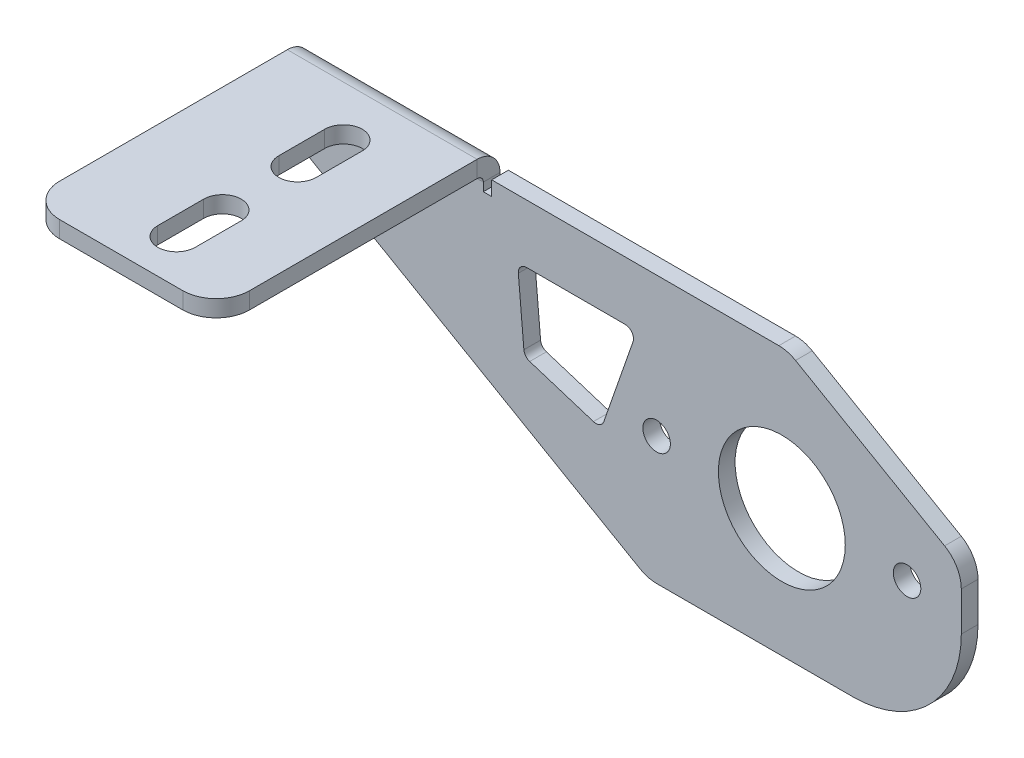
SolidWorks part; units mm, degrees
note: The reader was unsure of these and kept them because the rebuilt part matched: flange length of "边线-法兰1".
material "6061 合金"
ref_plane "前视基准面" through (0, 0, 0) normal (0, 0, 1) x (1, 0, 0)
ref_plane "上视基准面" through (0, 0, 0) normal (0, 1, 0) x (1, 0, 0)
ref_plane "右视基准面" through (0, 0, 0) normal (1, 0, 0) x (0, 0, -1)
sketch "草图1" plane through (0, 0, 0) normal (0, 0, 1) x (1, 0, 0)
  line L0 (0, 0) -> (0, -7.5)
  line L1 (0, -7.5) -> (42.4352, -32)
  line L2 (42.4352, -32) -> (80, -32)
  line L3 (80, -32) -> (80, -12)
  line L4 (80, -12) -> (59.2154, 0)
  line L5 (59.2154, 0) -> (0, 0)
  dimension "D1" = 7.5
  dimension "D2" = 20
  dimension "D3" = 80
  dimension "D4" = 150
  dimension "D5" = 120
  dimension "D6" = 32
base flange "基体-法兰1" sketch "草图1" thickness 2 reverse thickness direction no parameters "D1"=0.7366
sketch "草图6" plane through (0, 0, 0) normal (0, 0, 1) x (1, 0, 0)
  line L0 (80, -32) -> (80, -12) construction
  line L1 (42.4352, -32) -> (80, -32) construction
  circle A0 centre (58.5, -16.7) radius 7.6
  circle A1 centre (73.5, -16.7) radius 1.65
  circle A2 centre (43.5, -16.7) radius 1.65
  dimension "D1" = 15.2
  dimension "D4" = 3.3
  dimension "D5" = 3.3
  dimension "D2" = 21.5
  dimension "D3" = 15.3
  dimension "D6" = 15
  dimension "D7" = 15
extrude "切除-拉伸1" cut sketch "草图6" against normal blind 10 normal cut yes
edge flange "边线-法兰1" sketch "草图9" flange angle 90 flange length 34 flange position material outside bend radius 0.7366 thickness 2 relief rectangular parameters "D6"=10
sketch "草图9" plane through (0, 0, 0) normal (0, 1, 0) x (-1, 0, 0)
  line L0 (-59.2154, 0) -> (0, 0) construction
  line L2 (-22.74, 0) -> (-22.74, 32)
  line L3 (-22.74, 32) -> (0, 32)
  line L4 (0, 32) -> (0, 0)
  line L5 (-22.74, 0) -> (0, 0)
  dimension "D1" = 22.74
  dimension "D2" = 32
bend "边线折弯1" bend radius 0.7366 bend angle 90 parameters "D5"=1
sketch "草图12" plane through (0, 2, 0) normal (0, 1, 0) x (1, 0, 0)
  line L0 (12.74, -32) -> (12.74, -0.7366) construction
  line L1 (0, -32) -> (22.74, -32) construction
  line L2 (0, -0.7366) -> (22.74, -0.7366) construction
  line L3 (22.74, -32) -> (22.74, -0.7366) construction
  line L4 (12.74, -26.75) -> (12.74, -21.25) construction
  line L5 (10.49, -26.75) -> (10.49, -21.25)
  line L6 (14.99, -26.75) -> (14.99, -21.25)
  line L7 (12.74, -12.25) -> (12.74, -6.75) construction
  line L8 (10.49, -12.25) -> (10.49, -6.75)
  line L9 (14.99, -12.25) -> (14.99, -6.75)
  arc A0 (10.49, -26.75) -> (14.99, -26.75) centre (12.74, -26.75) ccw
  arc A1 (14.99, -21.25) -> (10.49, -21.25) centre (12.74, -21.25) ccw
  arc A2 (10.49, -12.25) -> (14.99, -12.25) centre (12.74, -12.25) ccw
  arc A3 (14.99, -6.75) -> (10.49, -6.75) centre (12.74, -6.75) ccw
  point P10 (12.74, -24)
  point P15 (12.74, -9.5)
  point P22 (12.74, -19)
  point P23 (12.74, -14.5)
  dimension "D4" = 2.25
  dimension "D5" = 2.25
  dimension "D1" = 10
  dimension "D2" = 5.5
  dimension "D3" = 5.5
  dimension "D6" = 5.25
  dimension "D7" = 4.5
extrude "切除-拉伸2" cut sketch "草图12" against normal blind 10 normal cut yes
fillet "圆角1" radius 4 6 edges at (59.2154, 0, -1) (80, -12, -1) (42.4352, -32, -1) (0, -7.5, -1) (22.74, 1, 32) (0, 1, 32)
unfold "展开1" [suppressed]
sketch "草图12-1" plane through (0, 1.2546, -2) normal (0, 0, -1) x (1, 0, 0)
  line L0 (12.74, -32) -> (12.74, -0.7366) construction
  line L1 (4, -32) -> (18.74, -32) construction
  line L3 (22.74, -28) -> (22.74, -0.7366) construction
  line L4 (12.74, -26.75) -> (12.74, -21.25) construction
  line L5 (10.49, -26.75) -> (10.49, -21.25)
  line L6 (14.99, -26.75) -> (14.99, -21.25)
  line L7 (12.74, -12.25) -> (12.74, -6.75) construction
  line L8 (10.49, -12.25) -> (10.49, -6.75)
  line L9 (14.99, -12.25) -> (14.99, -6.75)
  arc A0 (10.49, -26.75) -> (14.99, -26.75) centre (12.74, -26.75) ccw
  arc A1 (14.99, -21.25) -> (10.49, -21.25) centre (12.74, -21.25) ccw
  arc A2 (10.49, -12.25) -> (14.99, -12.25) centre (12.74, -12.25) ccw
  arc A3 (14.99, -6.75) -> (10.49, -6.75) centre (12.74, -6.75) ccw
  point P10 (12.74, -24)
  point P15 (12.74, -9.5)
  dimension "D4" = 2.25
  dimension "D5" = 2.25
  dimension "D1" = 10
  dimension "D2" = 5.5
  dimension "D3" = 5.5
  dimension "D6" = 5.25
sketch "草图14" plane through (0, 0, -2) normal (0, 0, -1) x (-1, 0, 0)
  line L0 (-36.8593, -19.275) -> (-27.6593, -16.3642)
  line L1 (-27.6593, -16.3642) -> (-26.84, -7)
  line L2 (-26.84, -7) -> (-41.14, -7)
  line L3 (-41.14, -7) -> (-36.8593, -19.275)
  line L4 (-58.1436, 0) -> (-23.74, 0) construction
  line L5 (-22.74, -1.7366) -> (-22.74, -0.7366) construction
  dimension "D1" = 14.3
  dimension "D2" = 85
  dimension "D3" = 9.4
  dimension "D4" = 13
  dimension "D5" = 7
  dimension "D6" = 4.1
  dimension "D7" = 9.2
extrude "切除-拉伸3" cut sketch "草图14" against normal blind 10 normal cut yes
fillet "圆角2" radius 1 4 edges at (26.84, -7, -1) (27.6593, -16.3642, -1) (36.8593, -19.275, -1) (41.14, -7, -1)
fillet "圆角3" radius 13 1 edges at (80, -32, -1)
sketch "折弯-线1" plane through (0, 0, 0) normal (0, 1, 0) x (1, 0, 0)
sketch "边界框1" plane through (0, 0, 0) normal (0, 1, 0) x (1, 0, 0)
sheet metal parameters "钣金1" thickness 2 parameters "D1"=0.7366
flat pattern "平板型式1"
sketch "折弯-线2" plane through (0, 0, 0) normal (0, 1, 0) x (1, 0, 0)
sketch3d "边界框2"
  line L0 (0, -28.2, 0) -> (-70.5, -28.2, 0) construction
  line L1 (0, 0, 0) -> (-70.5, 0, 0) construction
  line L2 (0, -28.2, 0) -> (0, 0, 0) construction
  line L3 (-70.5, -28.2, 0) -> (-70.5, 0, 0) construction
sheet metal parameters "钣金2" thickness 2 parameters "D1"=0.7366
flat pattern "平板型式1"
sketch "折弯-线2" plane through (0, 0, 0) normal (0, 1, 0) x (1, 0, 0)
sketch3d "边界框2"
  line L0 (0, -28.2, 0) -> (70.5, -28.2, 0) construction
  line L1 (0, 0, 0) -> (70.5, 0, 0) construction
  line L2 (0, -28.2, 0) -> (0, 0, 0) construction
  line L3 (70.5, -28.2, 0) -> (70.5, 0, 0) construction
sheet metal parameters "钣金3" thickness 2 parameters "D1"=0.7366
flat pattern "平板型式1"
sketch "折弯-线2" plane through (0, 0, 0) normal (0, 0, 1) x (1, 0, 0)
  line L0 (22.74, 0.6273) -> (0, 0.6273) construction
  line L1 (22.74, 0.6273) -> (0, 0.6273) construction
sketch3d "边界框2"
  line L0 (10.556, 44.5955, 0) -> (78.9782, -19.0914, 0) construction
  line L1 (-20.325, 11.4184, 0) -> (48.0972, -52.2685, 0) construction
  line L2 (10.556, 44.5955, 0) -> (-20.325, 11.4184, 0) construction
  line L3 (78.9782, -19.0914, 0) -> (48.0972, -52.2685, 0) construction
bend of the flat pattern "展平-<边线折弯1>1"
sheet metal parameters "钣金4" thickness 2 parameters "D1"=0.7366
flat pattern "平板型式1"
sketch "折弯-线2" plane through (0, 0, 0) normal (0, 0, 1) x (1, 0, 0)
  line L0 (22.74, 0.6273) -> (0, 0.6273) construction
  line L1 (22.74, 0.6273) -> (0, 0.6273) construction
sketch3d "边界框2"
  line L0 (8.6426, 41.9629, 0) -> (88.2026, -18.5672, 0) construction
  line L1 (-18.2039, 6.6763, 0) -> (61.3561, -53.8538, 0) construction
  line L2 (8.6426, 41.9629, 0) -> (-18.2039, 6.6763, 0) construction
  line L3 (88.2026, -18.5672, 0) -> (61.3561, -53.8538, 0) construction
bend of the flat pattern "展平-<边线折弯1>1"
sheet metal parameters "钣金5" thickness 2 parameters "D1"=0.7366
flat pattern "平板型式1"
sketch "折弯-线2" plane through (0, 0, 0) normal (0, 0, 1) x (1, 0, 0)
  line L0 (22.74, 0.6273) -> (0, 0.6273) construction
  line L1 (22.74, 0.6273) -> (0, 0.6273) construction
sketch3d "边界框2"
  line L0 (8.6426, 41.9629, 0) -> (85.3279, -16.3801, 0) construction
  line L1 (-18.2038, 6.6763, 0) -> (58.4815, -51.6667, 0) construction
  line L2 (8.6426, 41.9629, 0) -> (-18.2038, 6.6763, 0) construction
  line L3 (85.3279, -16.3801, 0) -> (58.4815, -51.6667, 0) construction
bend of the flat pattern "展平-<边线折弯1>1"
